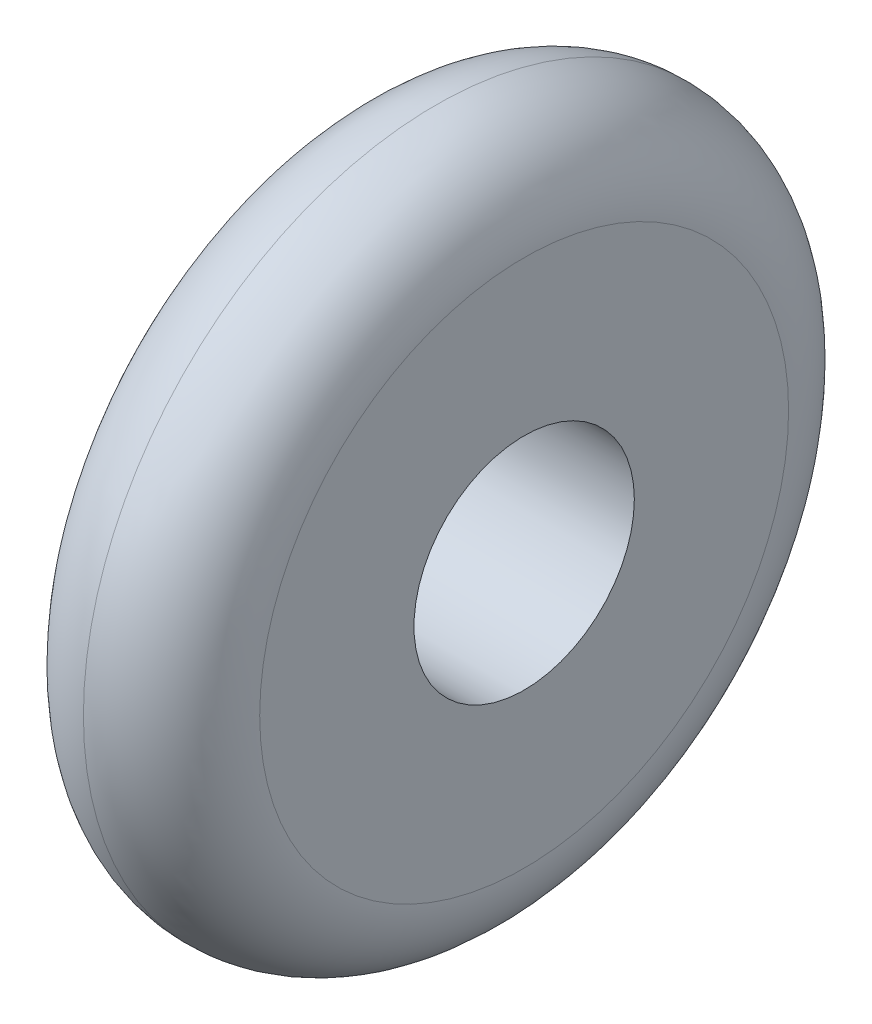
SolidWorks part; units mm, degrees
ref_plane "Front Plane" through (0, 0, 0) normal (0, 0, 1) x (1, 0, 0)
ref_plane "Top Plane" through (0, 0, 0) normal (0, 1, 0) x (1, 0, 0)
ref_plane "Right Plane" through (0, 0, 0) normal (1, 0, 0) x (0, 0, -1)
ref_plane "Plane1" through (20, 0, 0) normal (1, 0, 0) x (0, 0, -1)
sketch "Sketch1" plane through (0, 0, 0) normal (1, 0, 0) x (0, 0, -1)
  circle A0 centre (0, 0) radius 40
  dimension "D1" = 80
extrude "Boss-Extrude1" add sketch "Sketch1" along normal blind 20
fillet "Fillet2" radius 10 2 edges at (0, 0, -40) (20, 0, -40)
sketch "Sketch2" plane through (20, 0, 0) normal (1, 0, 0) x (0, 0, -1)
  circle A0 centre (0, 0) radius 12.5
  dimension "D1" = 25
extrude "Cut-Extrude1" cut sketch "Sketch2" against normal blind 20
